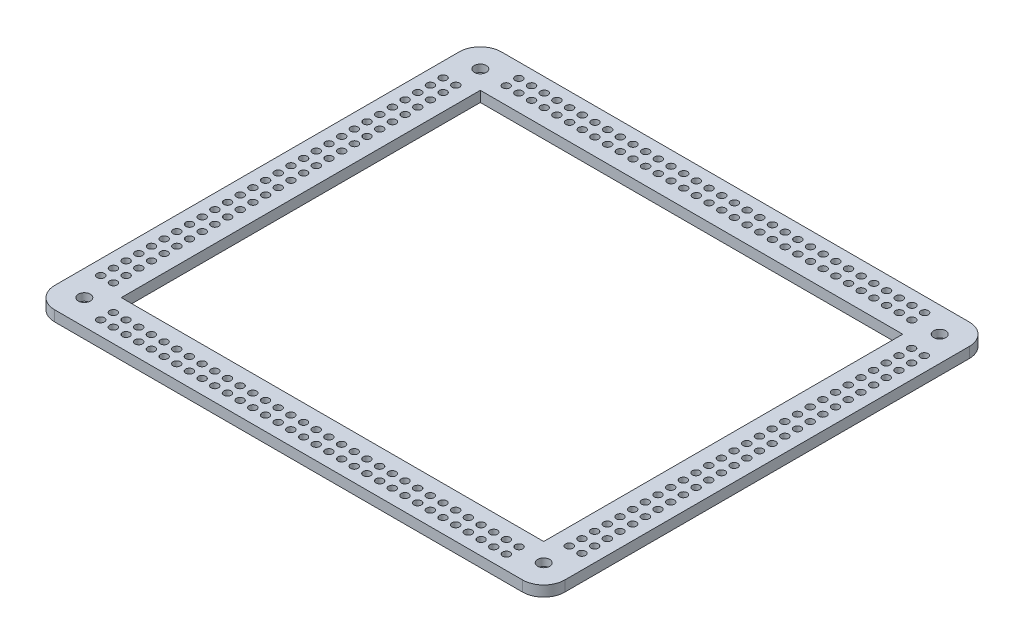
SolidWorks part; units mm, degrees
ref_plane "Front Plane" through (0, 0, 0) normal (0, 0, 1) x (1, 0, 0)
ref_plane "Top Plane" through (0, 0, 0) normal (0, 1, 0) x (1, 0, 0)
ref_plane "Right Plane" through (0, 0, 0) normal (1, 0, 0) x (0, 0, -1)
sketch "Sketch1" plane through (0, 0, 0) normal (0, 1, 0) x (1, 0, 0)
  line L1 (-99.95, 84.95) -> (99.95, 84.95)
  line L2 (-99.95, 84.95) -> (-99.95, -84.95)
  line L3 (-99.95, -84.95) -> (99.95, -84.95)
  line L4 (99.95, 84.95) -> (99.95, -84.95)
  line L5 (-120.7, 105.7) -> (120.7, 105.7)
  line L6 (-120.7, 105.7) -> (-120.7, -105.7)
  line L7 (-120.7, -105.7) -> (120.7, -105.7)
  line L8 (120.7, 105.7) -> (120.7, -105.7)
  point P4 (-99.95, 0)
  point P6 (0, 84.95)
  point P11 (0, -105.7)
  point P12 (-120.7, 0)
  dimension "D1" = 199.9
  dimension "D2" = 169.9
  dimension "D3" = 20.75
  dimension "D4" = 20.75
extrude "Boss-Extrude1" add sketch "Sketch1" along normal blind 5
fillet "Fillet1" radius 10 4 edges at (-120.7, 2.5, -105.7) (120.7, 2.5, -105.7) (120.7, 2.5, 105.7) (-120.7, 2.5, 105.7)
sketch "Sketch2" plane through (0, 0, 0) normal (0, -1, 0) x (1, 0, 0)
  line L0 (-110.7, 105.7) -> (110.7, 105.7) construction
  line L1 (-120.7, -95.7) -> (-120.7, 95.7) construction
  circle A0 centre (-108.7, 93.7) radius 5.85
  dimension "D3" = 11.7
  dimension "D1" = 12
  dimension "D2" = 12
extrude "Boss-Extrude2" add sketch "Sketch2" along normal blind 2.5
sketch "Sketch3" plane through (0, 5, 0) normal (0, 1, 0) x (1, 0, 0)
  line L2 (-120.7, 95.7) -> (-120.7, -95.7) construction
  line L3 (-110.7, -105.7) -> (110.7, -105.7) construction
  circle A0 centre (-108.7, -93.7) radius 1.55
  point P2 (-108.7, -95.5911)
  point P4 (0, 0)
  point P6 (-120.7, 93.5096)
  dimension "D1" = 3.1
  dimension "D2" = 12
  dimension "D3" = 12
extrude "Cut-Extrude1" cut sketch "Sketch3" against normal blind 7.5
sketch "Sketch4" plane through (0, 5, 0) normal (0, 1, 0) x (1, 0, 0)
  circle A0 centre (-108.7, -93.7) radius 2.85
  dimension "D1" = 5.7
extrude "Cut-Extrude2" cut sketch "Sketch4" against normal blind 3.5
mirror "Mirror3" about plane through (0, 0, 0) normal (1, 0, 0) of "Cut-Extrude1", "Cut-Extrude2", "Boss-Extrude2"
mirror "Mirror4" about plane through (0, 0, 0) normal (0, 0, 1) of "Mirror3"
sketch "Sketch5" plane through (0, 5, 0) normal (0, 1, 0) x (1, 0, 0)
  line L0 (-99.95, -84.95) -> (99.95, -84.95) construction
  line L1 (-120.7, 95.7) -> (-120.7, -95.7) construction
  circle A0 centre (-95.7, -92.95) radius 1.75
  circle A1 centre (-95.7, -98.95) radius 1.75
  circle A4 centre (-89.7, -92.95) radius 1.75
  circle A5 centre (-89.7, -98.95) radius 1.75
  circle A7 centre (-83.7, -92.95) radius 1.75
  circle A8 centre (-83.7, -98.95) radius 1.75
  circle A10 centre (-77.7, -92.95) radius 1.75
  circle A11 centre (-77.7, -98.95) radius 1.75
  circle A13 centre (-71.7, -92.95) radius 1.75
  circle A14 centre (-71.7, -98.95) radius 1.75
  circle A16 centre (-65.7, -92.95) radius 1.75
  circle A17 centre (-65.7, -98.95) radius 1.75
  circle A19 centre (-59.7, -92.95) radius 1.75
  circle A20 centre (-59.7, -98.95) radius 1.75
  circle A22 centre (-53.7, -92.95) radius 1.75
  circle A23 centre (-53.7, -98.95) radius 1.75
  circle A25 centre (-47.7, -92.95) radius 1.75
  circle A26 centre (-47.7, -98.95) radius 1.75
  circle A28 centre (-41.7, -92.95) radius 1.75
  circle A29 centre (-41.7, -98.95) radius 1.75
  circle A31 centre (-35.7, -92.95) radius 1.75
  circle A32 centre (-35.7, -98.95) radius 1.75
  circle A34 centre (-29.7, -92.95) radius 1.75
  circle A35 centre (-29.7, -98.95) radius 1.75
  circle A37 centre (-23.7, -92.95) radius 1.75
  circle A38 centre (-23.7, -98.95) radius 1.75
  circle A40 centre (-17.7, -92.95) radius 1.75
  circle A41 centre (-17.7, -98.95) radius 1.75
  circle A43 centre (-11.7, -92.95) radius 1.75
  circle A44 centre (-11.7, -98.95) radius 1.75
  circle A46 centre (-5.7, -92.95) radius 1.75
  circle A47 centre (-5.7, -98.95) radius 1.75
  circle A49 centre (0.3, -92.95) radius 1.75
  circle A50 centre (0.3, -98.95) radius 1.75
  circle A52 centre (6.3, -92.95) radius 1.75
  circle A53 centre (6.3, -98.95) radius 1.75
  circle A55 centre (12.3, -92.95) radius 1.75
  circle A56 centre (12.3, -98.95) radius 1.75
  circle A58 centre (18.3, -92.95) radius 1.75
  circle A59 centre (18.3, -98.95) radius 1.75
  circle A61 centre (24.3, -92.95) radius 1.75
  circle A62 centre (24.3, -98.95) radius 1.75
  circle A64 centre (30.3, -92.95) radius 1.75
  circle A65 centre (30.3, -98.95) radius 1.75
  circle A67 centre (36.3, -92.95) radius 1.75
  circle A68 centre (36.3, -98.95) radius 1.75
  circle A70 centre (42.3, -92.95) radius 1.75
  circle A71 centre (42.3, -98.95) radius 1.75
  circle A73 centre (48.3, -92.95) radius 1.75
  circle A74 centre (48.3, -98.95) radius 1.75
  circle A76 centre (54.3, -92.95) radius 1.75
  circle A77 centre (54.3, -98.95) radius 1.75
  circle A79 centre (60.3, -92.95) radius 1.75
  circle A80 centre (60.3, -98.95) radius 1.75
  circle A82 centre (66.3, -92.95) radius 1.75
  circle A83 centre (66.3, -98.95) radius 1.75
  circle A85 centre (72.3, -92.95) radius 1.75
  circle A86 centre (72.3, -98.95) radius 1.75
  circle A88 centre (78.3, -92.95) radius 1.75
  circle A89 centre (78.3, -98.95) radius 1.75
  circle A91 centre (84.3, -92.95) radius 1.75
  circle A92 centre (84.3, -98.95) radius 1.75
  circle A94 centre (90.3, -92.95) radius 1.75
  circle A95 centre (90.3, -98.95) radius 1.75
  circle A97 centre (96.3, -92.95) radius 1.75
  circle A98 centre (96.3, -98.95) radius 1.75
  circle A135 centre (102.3, -92.95) radius 1.75 [skipped]
  circle A136 centre (102.3, -98.95) radius 1.75 [skipped]
  point P4 (-99.6217, -89.325)
  point P5 (-98.4735, -89.325)
  dimension "D1" = 3.5
  dimension "D2" = 25
  dimension "D5" = 8
  dimension "D6" = 34
extrude "Cut-Extrude3" cut sketch "Sketch5" against normal blind 5
mirror "Mirror5" about plane through (0, 0, 0) normal (0, 0, 1) of "Cut-Extrude3"
sketch "Sketch6" plane through (0, 5, 0) normal (0, 1, 0) x (1, 0, 0)
  line L1 (-120.7, 95.7) -> (-120.7, -95.7) construction
  circle A1 centre (-107.85, -80.75) radius 1.75
  circle A2 centre (-113.85, -80.75) radius 1.75
  circle A3 centre (-108.7, -93.7) radius 2.85 construction
  circle A5 centre (-107.85, -74.75) radius 1.75
  circle A6 centre (-113.85, -74.75) radius 1.75
  circle A8 centre (-107.85, -68.75) radius 1.75
  circle A9 centre (-113.85, -68.75) radius 1.75
  circle A11 centre (-107.85, -62.75) radius 1.75
  circle A12 centre (-113.85, -62.75) radius 1.75
  circle A14 centre (-107.85, -56.75) radius 1.75
  circle A15 centre (-113.85, -56.75) radius 1.75
  circle A17 centre (-107.85, -50.75) radius 1.75
  circle A18 centre (-113.85, -50.75) radius 1.75
  circle A20 centre (-107.85, -44.75) radius 1.75
  circle A21 centre (-113.85, -44.75) radius 1.75
  circle A23 centre (-107.85, -38.75) radius 1.75
  circle A24 centre (-113.85, -38.75) radius 1.75
  circle A26 centre (-107.85, -32.75) radius 1.75
  circle A27 centre (-113.85, -32.75) radius 1.75
  circle A29 centre (-107.85, -26.75) radius 1.75
  circle A30 centre (-113.85, -26.75) radius 1.75
  circle A32 centre (-107.85, -20.75) radius 1.75
  circle A33 centre (-113.85, -20.75) radius 1.75
  circle A35 centre (-107.85, -14.75) radius 1.75
  circle A36 centre (-113.85, -14.75) radius 1.75
  circle A38 centre (-107.85, -8.75) radius 1.75
  circle A39 centre (-113.85, -8.75) radius 1.75
  circle A41 centre (-107.85, -2.75) radius 1.75
  circle A42 centre (-113.85, -2.75) radius 1.75
  circle A44 centre (-107.85, 3.25) radius 1.75
  circle A45 centre (-113.85, 3.25) radius 1.75
  circle A47 centre (-107.85, 9.25) radius 1.75
  circle A48 centre (-113.85, 9.25) radius 1.75
  circle A50 centre (-107.85, 15.25) radius 1.75
  circle A51 centre (-113.85, 15.25) radius 1.75
  circle A53 centre (-107.85, 21.25) radius 1.75
  circle A54 centre (-113.85, 21.25) radius 1.75
  circle A56 centre (-107.85, 27.25) radius 1.75
  circle A57 centre (-113.85, 27.25) radius 1.75
  circle A59 centre (-107.85, 33.25) radius 1.75
  circle A60 centre (-113.85, 33.25) radius 1.75
  circle A62 centre (-107.85, 39.25) radius 1.75
  circle A63 centre (-113.85, 39.25) radius 1.75
  circle A65 centre (-107.85, 45.25) radius 1.75
  circle A66 centre (-113.85, 45.25) radius 1.75
  circle A68 centre (-107.85, 51.25) radius 1.75
  circle A69 centre (-113.85, 51.25) radius 1.75
  circle A71 centre (-107.85, 57.25) radius 1.75
  circle A72 centre (-113.85, 57.25) radius 1.75
  circle A74 centre (-107.85, 63.25) radius 1.75
  circle A75 centre (-113.85, 63.25) radius 1.75
  circle A77 centre (-107.85, 69.25) radius 1.75
  circle A78 centre (-113.85, 69.25) radius 1.75
  circle A80 centre (-107.85, 75.25) radius 1.75
  circle A81 centre (-113.85, 75.25) radius 1.75
  circle A83 centre (-107.85, 81.25) radius 1.75
  circle A84 centre (-113.85, 81.25) radius 1.75
  circle A116 centre (-107.85, 87.25) radius 1.75 [skipped]
  circle A117 centre (-113.85, 87.25) radius 1.75 [skipped]
  dimension "D4" = 12.95
  dimension "D1" = 6.85
  dimension "D2" = 6
  dimension "D7" = 29
extrude "Cut-Extrude4" cut sketch "Sketch6" against normal blind 5
mirror "Mirror6" about plane through (0, 0, 0) normal (1, 0, 0) of "Cut-Extrude4"
